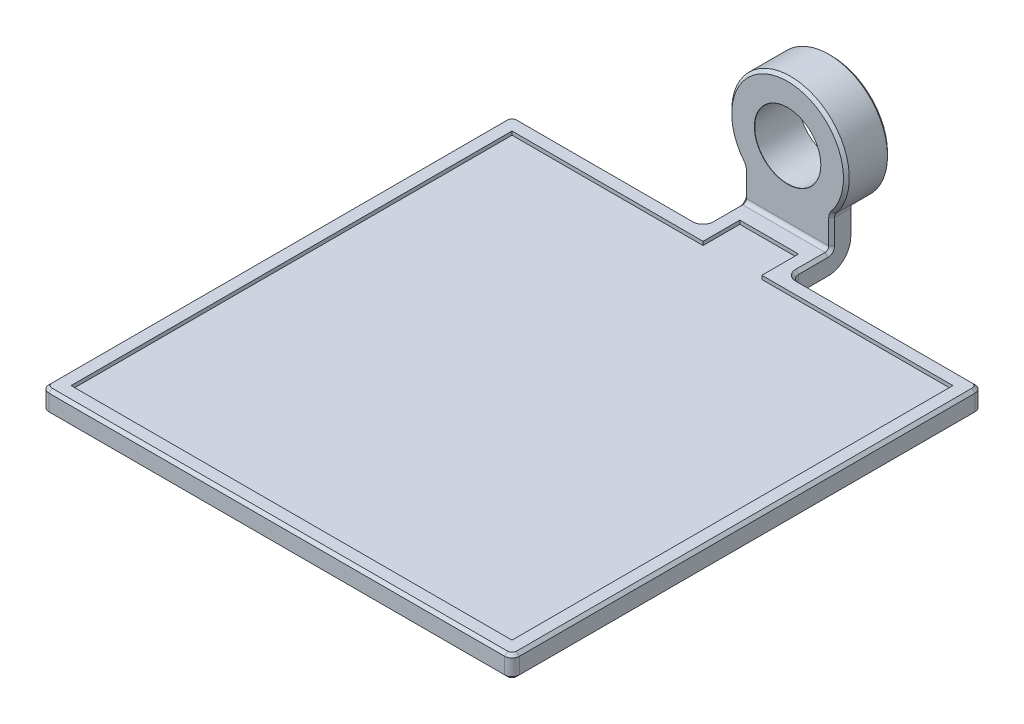
SolidWorks part; units mm, degrees
ref_plane "Front Plane" through (0, 0, 0) normal (0, 0, 1) x (1, 0, 0)
ref_plane "Top Plane" through (0, 0, 0) normal (0, 1, 0) x (1, 0, 0)
ref_plane "Right Plane" through (0, 0, 0) normal (1, 0, 0) x (0, 0, -1)
sketch "Sketch1" plane through (0, 0, 0) normal (0, 0, 1) x (1, 0, 0)
  circle A0 centre (0, 0) radius 8
  dimension "D1" = 16
extrude "Boss-Extrude1" add sketch "Sketch1" along normal blind 6
sketch "Sketch4" plane through (0, 0, 0) normal (1, 0, 0) x (0, 0, -1)
  line L0 (-6, -4.5) -> (-6, -9)
  line L1 (-6.5, -9.5) -> (-11.5, -9.5)
  line L2 (-3, -4.5) -> (-3, -9)
  line L3 (-6.5, -12.5) -> (-11.5, -12.5)
  line L4 (-3, -4.5) -> (-6, -4.5)
  line L5 (-6, 8) -> (-6, -8) construction
  line L6 (-6, -8) -> (0, -8) construction
  line L7 (-11.5, -9.5) -> (-11.5, -12.5)
  arc A0 (-6, -9) -> (-6.5, -9.5) centre (-6.5, -9) cw
  arc A1 (-3, -9) -> (-6.5, -12.5) centre (-6.5, -9) cw
  dimension "D1" = 5
  dimension "D2" = 0.5
  dimension "D3" = 4.5
  dimension "D5" = 3.5
  dimension "D4" = 3
extrude "Boss-Extrude2" add sketch "Sketch4" along normal mid plane 12
sketch "Sketch5" plane through (0, -9.5, 0) normal (0, 1, 0) x (1, 0, 0)
  line L0 (6, -11.5) -> (-6, -11.5) construction
  line L1 (32, -11.5) -> (-32, -11.5)
  line L2 (32, -11.5) -> (32, -75.5)
  line L3 (32, -75.5) -> (-32, -75.5)
  line L4 (-32, -11.5) -> (-32, -75.5)
  point P4 (0, -11.5)
  dimension "D1" = 64
extrude "Boss-Extrude3" add sketch "Sketch5" against normal up to surface (3 mm away) up to face at (0, -12.5, 9)
sketch "Sketch6" plane through (0, -9.5, 0) normal (0, 1, 0) x (1, 0, 0)
  line L16 (-4, -8.5) -> (-4, -13.5)
  line L17 (-4, -13.5) -> (-30, -13.5)
  line L18 (-30, -13.5) -> (-30, -73.5)
  line L19 (-30, -73.5) -> (30, -73.5)
  line L20 (30, -73.5) -> (30, -13.5)
  line L21 (30, -13.5) -> (4, -13.5)
  line L22 (4, -13.5) -> (4, -8.5)
  line L23 (4, -8.5) -> (-4, -8.5)
  line L24 (-4, -8.5) -> (-4, -13.5)
  line L25 (-4, -13.5) -> (-30, -13.5)
  line L26 (-30, -13.5) -> (-30, -73.5)
  line L27 (-30, -73.5) -> (30, -73.5)
  line L28 (30, -73.5) -> (30, -13.5)
  line L29 (30, -13.5) -> (4, -13.5)
  line L30 (4, -13.5) -> (4, -8.5)
  line L31 (4, -8.5) -> (-4, -8.5)
  dimension "D1" = 2
extrude "Cut-Extrude1" cut sketch "Sketch6" against normal blind 0.5
fillet "Fillet2" radius 1 8 edges at (-6, -5.2915, 4.5) (6, -5.2915, 4.5) (6, -11, 11.5) (32, -11, 11.5) (32, -11, 75.5) (-32, -11, 75.5) (-6, -11, 11.5) (-32, -11, 11.5)
hole_wizard "M8 Clearance Hole1" positions "Sketch7" profile "Sketch8" hole size "M8" standard "ANSI Metric" end condition up to next
sketch "Sketch7" plane through (0, 0, 6) normal (0, 0, 1) x (1, 0, 0)
  point P0 (0, 0)
sketch "Sketch8" plane through (0, 0, 6) normal (1, 0, 0) x (0, -1, 0)
  line L0 (0, 0) -> (0, 6)
  line L1 (0, 6) -> (4.5, 6)
  line L2 (4.5, 6) -> (4.5, 0.025)
  line L3 (4.5, 0.025) -> (4.525, 0)
  line L5 (4.525, 0) -> (0, 0)
  line L6 (-4.5, 0.025) -> (-4.525, 0) construction
  line L11 (0, -6.35) -> (0, 107.95) construction
  dimension "Thru Hole Dia." = 9
  dimension "Thru Hole Depth" = 6
  dimension "Near C'Sink Dia." = 9.05
  dimension "Near C'Sink Angle" = 90
chamfer "Chamfer1" distance 0.4 angle 45 40 edges at (6.0572, -5.3235, 3) (6, -7.3284, 3) (6, -11.4749, 4.0251) (6, -12.5, 8.5) (6.2929, -12.5, 11.2071) (19, -12.5, 11.5) (31.7071, -12.5, 11.7929) (32, -12.5, 43.5) (31.7071, -12.5, 75.2071) (0, -12.5, 75.5) (-31.7071, -12.5, 75.2071) (-32, -12.5, 43.5) (-31.7071, -12.5, 11.7929) (-19, -12.5, 11.5) (-6.2929, -12.5, 11.2071) (-6.0572, -5.3235, 3) (-6, -12.5, 8.5) (-6, -7.3284, 3) (-6, -11.4749, 4.0251) (0, -9.5, 75.5) (31.7071, -9.5, 75.2071) (-31.7071, -9.5, 75.2071) (32, -9.5, 43.5) (-32, -9.5, 43.5) (31.7071, -9.5, 11.7929) (-31.7071, -9.5, 11.7929) (19, -9.5, 11.5) (-19, -9.5, 11.5) (6.2929, -9.5, 11.2071) (-6.2929, -9.5, 11.2071) (6, -9.5, 8.5) (-6, -9.5, 8.5) (6, -9.3536, 6.1464) (-6, -9.3536, 6.1464) (6, -7.3284, 6) (-6, -7.3284, 6) (6.0572, -5.3235, 6) (-6.0572, -5.3235, 6) (0, 8, 6) (8, 0, 0)
